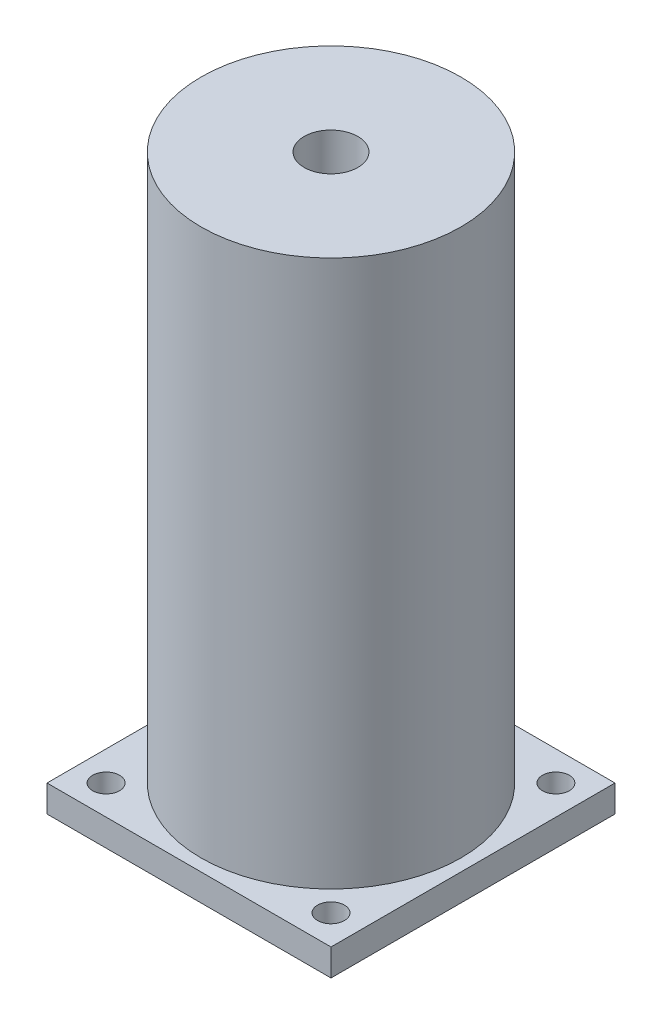
SolidWorks part; units mm, degrees
ref_plane "Front Plane" through (0, 0, 0) normal (0, 0, 1) x (1, 0, 0)
ref_plane "Top Plane" through (0, 0, 0) normal (0, 1, 0) x (1, 0, 0)
ref_plane "Right Plane" through (0, 0, 0) normal (1, 0, 0) x (0, 0, -1)
sketch "Sketch1" plane through (0, 0, 0) normal (0, 1, 0) x (1, 0, 0)
  line L1 (-15.85, -15.85) -> (15.85, -15.85)
  line L2 (-15.85, -15.85) -> (-15.85, 15.85)
  line L3 (-15.85, 15.85) -> (15.85, 15.85)
  line L4 (15.85, -15.85) -> (15.85, 15.85)
  line L5 (-15.85, -15.85) -> (15.85, 15.85) construction
  line L6 (-15.85, 15.85) -> (15.85, -15.85) construction
  point P0 (0, 0)
  dimension "D1" = 31.7
  dimension "D2" = 31.7
extrude "Boss-Extrude1" add sketch "Sketch1" along normal blind 3
sketch "Sketch2" plane through (0, 3, 0) normal (0, 1, 0) x (1, 0, 0)
  circle A0 centre (0, 0) radius 14.5
  dimension "D1" = 29
extrude "Boss-Extrude2" add sketch "Sketch2" along normal blind 61
sketch "Sketch3" plane through (0, 0, 0) normal (0, -1, 0) x (1, 0, 0)
  line L0 (-15.85, 15.85) -> (15.85, -15.85) construction
  line L1 (15.85, 15.85) -> (-15.85, -15.85) construction
  circle A0 centre (0, 0) radius 17.75 construction
  dimension "D1" = 35.5
hole_wizard "Ø3.0mm Dowel Hole1" positions "Sketch4" profile "Sketch5" hole size "Ø3.0" standard "ANSI Metric" end condition through all
sketch "Sketch4" plane through (0, 0, 0) normal (0, -1, 0) x (-1, 0, 0)
  line L0 (15.85, -15.85) -> (-15.85, 15.85) construction
  line L1 (-15.85, -15.85) -> (15.85, 15.85) construction
  circle A0 centre (0, 0) radius 17.75 construction
  point P0 (12.5511, -12.5511)
  point P6 (-12.5511, -12.5511)
  point P10 (12.5511, 12.5511)
  point P12 (-12.5511, 12.5511)
sketch "Sketch5" plane through (-12.5511, 0, 12.5511) normal (1, 0, 0) x (0, 0, -1)
  line L0 (0, 0) -> (0, 64)
  line L1 (0, 64) -> (1.5, 64)
  line L2 (1.5, 64) -> (1.5, 0)
  line L5 (1.5, 0) -> (0, 0)
  line L11 (0, -6.35) -> (0, 107.95) construction
  dimension "Thru Hole Dia." = 3
  dimension "Thru Hole Depth" = 64
ref_axis "Optic axis" through (0, 75.3502, 0) along (0, -1, 0)
ref_plane "Maximum extent 1" through (0, 0, -34.15) normal (0, 0, 1) x (1, 0, 0)
ref_plane "Maximum extent 2" through (34.15, 0, 0) normal (-1, 0, 0) x (0, 0, 1)
sketch "Sketch6" plane through (0, 64, 0) normal (0, 1, 0) x (1, 0, 0)
  circle A0 centre (0, 0) radius 3
  dimension "D1" = 6
extrude "Cut-Extrude1" cut sketch "Sketch6" against normal through all
